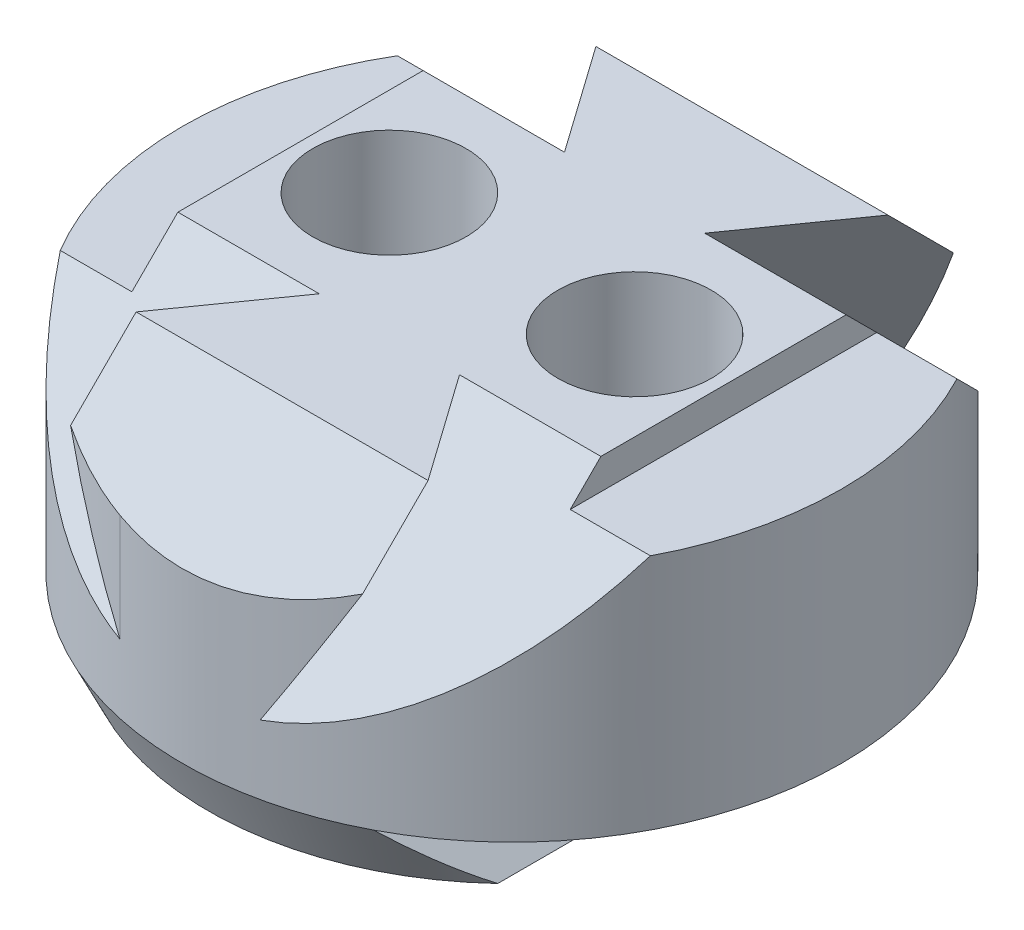
SolidWorks part; units mm, degrees
ref_plane "Front Plane" through (0, 0, 0) normal (0, 0, 1) x (1, 0, 0)
ref_plane "Top Plane" through (0, 0, 0) normal (0, 1, 0) x (1, 0, 0)
ref_plane "Right Plane" through (0, 0, 0) normal (1, 0, 0) x (0, 0, -1)
sketch "Sketch1" plane through (0, 0, 0) normal (0, 1, 0) x (1, 0, 0)
  circle A0 centre (0, 0) radius 21.5
  dimension "D1" = 43
extrude "Boss-Extrude1" add sketch "Sketch1" against normal blind 4
sketch "Sketch2" plane through (0, 0, 0) normal (0, 1, 0) x (1, 0, 0)
  circle A0 centre (0, 0) radius 5.875
  dimension "D1" = 11.75
extrude "Boss-Extrude2" add sketch "Sketch2" along normal blind 65
sketch "Sketch3" plane through (0, 0, 0) normal (0, 1, 0) x (1, 0, 0)
  line L0 (0, 0) -> (0, 21.5) construction
  line L1 (0, 21.5) -> (0, -21.5) construction
  circle A0 centre (0, 0) radius 21.5 construction
ref_plane "Plane1" through (0, 15.5, 0) normal (0, 1, 0) x (1, 0, 0)
sketch "Sketch5" plane through (0, 0, 0) normal (1, 0, 0) x (0, 0, -1)
  line L4 (21.5, 0) -> (-21.5, 0) construction
  line L5 (6, 0) -> (0, 0) construction
  line L8 (21.5, 0) -> (0, 0)
  line L10 (-21.5, 0) -> (0, 0)
  line L11 (21.5, 0) -> (6, 15.5)
  line L12 (23.65, 15.5) -> (-23.65, 15.5) construction
  line L13 (6, 15.5) -> (-6, 15.5)
  line L14 (-6, 15.5) -> (-21.5, 0)
  dimension "D1" = 21.5
  dimension "D2" = 15.5
  dimension "D3" = 15.5
extrude "Boss-Extrude3" add sketch "Sketch5" along normal up to surface and the other way up to surface up to face at (0, -4, 21.5) other way up to face at (0, -4, 21.5)
ref_plane "Plane2" through (0, 4.75, -4.75) normal (0, 0.7071, -0.7071) x (-1, 0, 0)
ref_plane "Plane3" through (0, 4.75, 4.75) normal (0, -0.7071, -0.7071) x (-1, 0, 0)
sketch "Sketch6" plane through (0, 4.75, 4.75) normal (0, -0.7071, -0.7071) x (-1, 0, 0)
  line L0 (0, 15.2028) -> (4.5753, 15.2028)
  line L1 (20.6458, 15.2028) -> (-20.6458, 15.2028) construction
  line L2 (4.5753, 15.2028) -> (9.525, 20.1525)
  line L3 (9.525, 20.1525) -> (0, 20.1525)
  line L4 (0, 20.1525) -> (-9.525, 20.1525)
  line L5 (-9.525, 20.1525) -> (-4.5753, 15.2028)
  line L6 (-4.5753, 15.2028) -> (0, 15.2028)
  dimension "D1" = 7
  dimension "D2" = 45
  dimension "D3" = 45
  dimension "D4" = 9.525
ref_plane "Plane4" through (0, 0, 6) normal (0, 0, 1) x (1, 0, 0)
ref_plane "Plane5" through (0, 0, -6) normal (0, 0, 1) x (1, 0, 0)
sketch "Sketch10" plane through (0, 4.75, -4.75) normal (0, 0.7071, -0.7071) x (-1, 0, 0)
  line L14 (0, 15.2028) -> (-4.5753, 15.2028)
  line L15 (20.6458, 15.2028) -> (-20.6458, 15.2028) construction
  line L16 (-4.5753, 15.2028) -> (-9.525, 20.1525)
  line L18 (9.525, 20.1525) -> (4.5753, 15.2028)
  line L19 (4.5753, 15.2028) -> (0, 15.2028)
  line L20 (9.525, 20.1525) -> (0, 20.1525)
  line L21 (0, 20.1525) -> (-9.525, 20.1525)
  dimension "D1" = 45
  dimension "D2" = 9.525
  dimension "D3" = 7
  dimension "D4" = 45
sketch "Sketch11" plane through (0, 0, 6) normal (0, 0, 1) x (1, 0, 0)
  line L0 (0, 65) -> (0, 15.5) construction
  line L1 (5.875, 65) -> (-5.875, 65) construction
  line L2 (0, 65) -> (0, 15.5) construction
sketch "Sketch12" plane through (0, 15.5, 0) normal (0, 1, 0) x (1, 0, 0)
  line L0 (-20.6458, 6) -> (20.6458, 6)
  line L1 (20.6458, -6) -> (-20.6458, -6)
  arc A0 (-20.6458, 6) -> (-20.6458, -6) centre (0, 0) ccw
  arc A2 (20.6458, 6) -> (20.6458, -6) centre (0, 0) cw
extrude "Boss-Extrude12" add sketch "Sketch6" along normal up to surface (21.9203 mm away) contours L3 L4 L5 L6 L0 L2 up to face at (0, -4, 21.5)
sketch "Sketch14" plane through (0, 15.5, 0) normal (0, 1, 0) x (1, 0, 0)
  circle A0 centre (0, 0) radius 5.875
  dimension "D1" = 11.75
ref_plane "Plane7" through (0, -4, 0) normal (0, -1, 0) x (-1, 0, 0)
sketch "Sketch16" plane through (0, -4, 0) normal (0, -1, 0) x (-1, 0, 0)
  circle A0 centre (0, 0) radius 1.5
sketch "Sketch17" plane through (0, 0, 0) normal (0, 0, 1) x (1, 0, 0)
  line L1 (-23.65, -4) -> (23.65, -4) construction
  line L2 (0, -4) -> (5, -4)
  line L3 (0, -4) -> (0, 6)
  line L4 (0, 6) -> (5, -4)
revolve "Cut-Revolve1" cut sketch "Sketch17" angle 360 about L3
extrude "Boss-Extrude13" add sketch "Sketch10" against normal up to surface (13.8239 mm away) contours L21 L16 L14 L19 L18 L20 up to face at (0, -4, 21.5)
extrude "Cut-Extrude3" cut sketch "Sketch14" along normal blind 10 and the other way blind 2 flip side to cut contours A0
ref_plane "Plane8" through (0, 13.5, 0) normal (0, 1, 0) x (1, 0, 0)
sketch "Sketch18" plane through (0, 0, 0) normal (1, 0, 0) x (0, 0, -1)
  line L0 (0, -4) -> (21.5, -4)
  line L1 (-23.65, -4) -> (23.65, -4) construction
  line L2 (21.5, -4) -> (21.5, 7) construction
  line L3 (21.5, -4) -> (0, -49)
  line L4 (0, -49) -> (0, -4)
  dimension "D1" = 45
sketch "Sketch19" plane through (0, 13.5, 0) normal (0, 1, 0) x (1, 0, 0)
  line L0 (0, 0) -> (11, 0) construction
  line L1 (0, 21.5) -> (0, -21.5) construction
  line L2 (11, 0) -> (11, 8)
  line L3 (19.9562, 8) -> (4.5753, 8) construction
  line L4 (11, 0) -> (11, -8)
  line L5 (4.5753, -8) -> (19.9562, -8) construction
  line L6 (0, 0) -> (-11, 0) construction
  line L7 (-11, 0) -> (-11, 8)
  line L8 (-4.5753, 8) -> (-19.9562, 8) construction
  line L9 (-11, 0) -> (-11, -8)
  line L10 (-19.9562, -8) -> (-4.5753, -8) construction
sketch "Sketch20" plane through (0, 0, 0) normal (0, 0, 1) x (1, 0, 0)
  line L0 (0, 13.5) -> (0, 25.5)
  line L1 (0, 13.5) -> (-11, 13.5) construction
  line L2 (0, 13.5) -> (11, 13.5) construction
  line L3 (0, 65) -> (0, 15.5) construction
  line L4 (0, 25.5) -> (-11, 13.5)
  line L5 (0, 25.5) -> (11, 13.5)
  line L6 (-5.875, 65) -> (-5.875, 13.5) construction
  line L7 (5.875, 13.5) -> (5.875, 65) construction
  line L8 (11, 13.5) -> (21.5, 2.0455)
  line L9 (21.5, -4) -> (21.5, 13.5) construction
  point P11 (-5.875, 19.0909)
  point P15 (5.875, 19.0909)
ref_plane "Plane9" through (0, 13.5, 0) normal (-0.6757, -0.7372, 0) x (0, 0, 1)
ref_plane "Plane10" through (0, 13.5, 0) normal (0.6757, -0.7372, 0) x (0, 0, -1)
ref_plane "Plane11" through (6.8269, 7.4475, 0) normal (-0.6757, -0.7372, 0) x (0, 0, 1)
sketch "Sketch22" plane through (6.8269, 7.4475, 0) normal (-0.6757, -0.7372, 0) x (0, 0, 1)
  line L0 (0, 17.231) -> (15, 17.231)
  line L1 (15, 17.231) -> (15, 27.3886)
  line L2 (15, 27.3886) -> (-15, 27.3886)
  line L3 (-15, 27.3886) -> (-15, 17.231)
  line L4 (-15, 17.231) -> (0, 17.231)
ref_plane "Plane12" through (-6.8269, 7.4475, 0) normal (0.6757, -0.7372, 0) x (-0.7372, -0.6757, 0)
sketch "Sketch23" plane through (-6.8269, 7.4475, 0) normal (0.6757, -0.7372, 0) x (-0.7372, -0.6757, 0)
  line L0 (-17.231, 0) -> (-17.231, 15)
  line L1 (-17.231, 15) -> (-27.231, 15)
  line L2 (-27.231, 15) -> (-27.231, -15)
  line L3 (-27.231, -15) -> (-17.231, -15)
  line L4 (-17.231, -15) -> (-17.231, 0)
sketch "Sketch24" plane through (0, 0, 0) normal (0, 0, 1) x (1, 0, 0)
  line L0 (0, -4) -> (10, -4)
  line L1 (0, -4) -> (0, -49) construction
  line L2 (0, -49) -> (0, -4) construction
  line L3 (-23.65, -4) -> (23.65, -4) construction
  line L4 (10, -4) -> (13.5355, -7.5355)
  line L6 (0, -4) -> (-10, -4)
  line L7 (-10, -4) -> (-13.5355, -7.5355)
  line L8 (-13.5355, -7.5355) -> (13.5355, -7.5355)
  dimension "D1" = 10
  dimension "D2" = 10
  dimension "D3" = 5
  dimension "D4" = 45
  dimension "D5" = 5
extrude "Boss-Extrude15" add sketch "Sketch24" along normal up to surface and the other way up to surface up to face at (0, -4, 21.5) other way up to face at (0, -4, 21.5)
sketch "Sketch25" plane through (0, 0, 0) normal (1, 0, 0) x (0, 0, -1)
  line L0 (21.5, -4) -> (21.5, -7.5355)
  line L1 (21.5, -7.5355) -> (19.8108, -7.5355)
  line L2 (21.5, -4) -> (0, -49) construction
  line L3 (16.7045, -7.5355) -> (21.5, -7.5355) construction
  line L4 (19.8108, -7.5355) -> (21.5, -4)
  line L5 (0, -4) -> (0, -7.5355) construction
  line L6 (-16.7045, -7.5355) -> (16.7045, -7.5355) construction
revolve "Cut-Revolve2" cut sketch "Sketch25" angle 360 about L5
sketch "Sketch26" plane through (0, -7.5355, 0) normal (0, -1, 0) x (-1, 0, 0)
  circle A0 centre (0, 0) radius 5
sketch "Sketch29" plane through (0, 65, 0) normal (0, 1, 0) x (1, 0, 0)
  circle A0 centre (0, 0) radius 7.5081
  dimension "D1" = 15.0162
extrude "Cut-Extrude9" cut sketch "Sketch29" along direction (0, 1, 0) on the side against the normal up to surface (51.5 mm away) up to face at (0, 13.5, 5.875)
sketch "Sketch30" plane through (0, 13.5, 0) normal (0, 1, 0) x (1, 0, 0)
  line L0 (-23.65, 0) -> (23.65, 0) construction
  circle A0 centre (-8, 0) radius 5
  circle A1 centre (8, 0) radius 5
  dimension "D1" = 10
  dimension "D2" = 10
  dimension "D3" = 8
  dimension "D4" = 8
extrude "Cut-Extrude10" cut sketch "Sketch30" against normal blind 10
sketch "Sketch31" plane through (0, 0, -6) normal (0, 0, 1) x (1, 0, 0)
  line L0 (-19.9562, 13.5) -> (-21.5, 13.5) construction
  line L1 (21.5, 13.5) -> (13.8, 13.5)
  line L2 (21.5, 13.5) -> (21.5, 11.5)
  line L3 (21.5, 11.5) -> (13.8, 11.5)
  line L4 (13.8, 13.5) -> (13.8, 11.5)
  line L5 (-21.5, 13.5) -> (-13.8, 13.5)
  line L6 (-21.5, 13.5) -> (-21.5, 10.5)
  line L7 (-21.5, 10.5) -> (-13.8, 10.5)
  line L8 (-13.8, 13.5) -> (-13.8, 10.5)
  dimension "D1" = 7.7
  dimension "D2" = 2
  dimension "D3" = 7.7
  dimension "D4" = 3
extrude "Cut-Extrude13" cut sketch "Sketch31" against normal through all both and the other way through all
sketch "Sketch32" plane through (0, 13.5, 0) normal (0, 1, 0) x (1, 0, 0)
  line L1 (-1.3, 8) -> (1.3, 8)
  line L2 (-1.3, 8) -> (-1.3, -8)
  line L3 (-1.3, -8) -> (1.3, -8)
  line L4 (1.3, 8) -> (1.3, -8)
  line L5 (-1.3, 8) -> (1.3, -8) construction
  line L6 (-1.3, -8) -> (1.3, 8) construction
  point P0 (0, 0)
  dimension "D1" = 16
  dimension "D2" = 2.6
